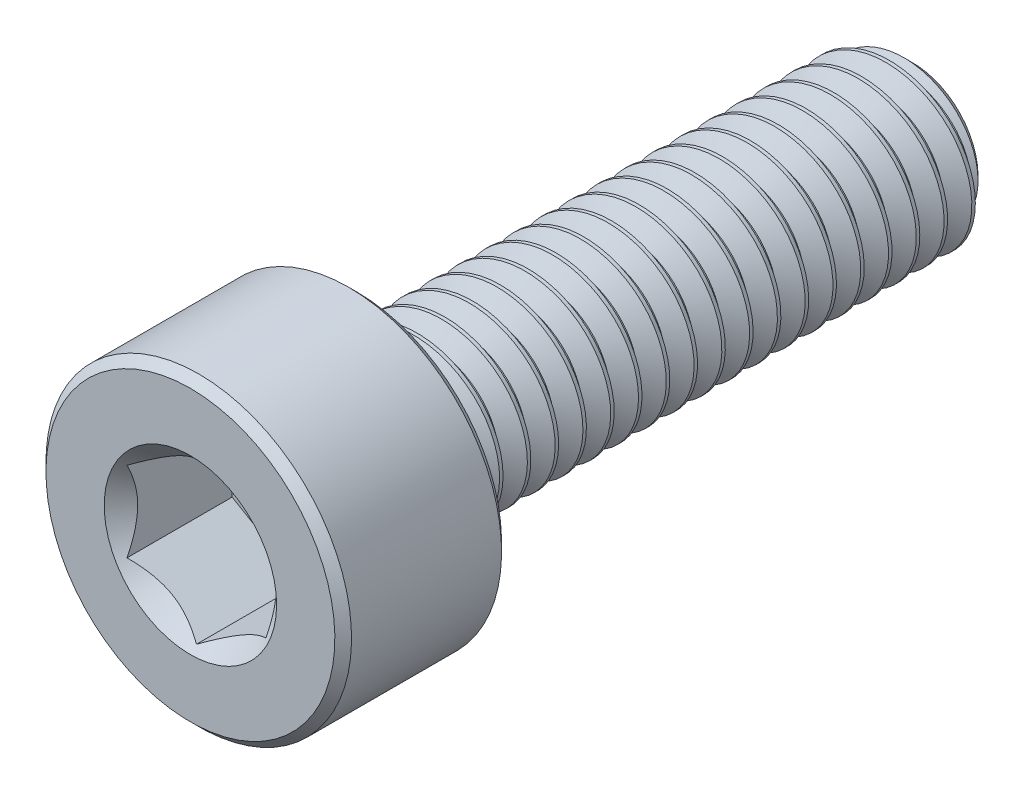
SolidWorks part; units mm, degrees
ref_plane "Front Plane" through (0, 0, 0) normal (0, 0, 1) x (1, 0, 0)
ref_plane "Top Plane" through (0, 0, 0) normal (0, 1, 0) x (1, 0, 0)
ref_plane "Right Plane" through (0, 0, 0) normal (1, 0, 0) x (0, 0, -1)
sketch "Sketch1" plane through (0, 0, 0) normal (1, 0, 0) x (0, 0, -1)
  line L0 (-6.5, 0) -> (6.5, 0) construction
  line L1 (6.5, 0) -> (6.5, 1.1752) construction
  line L2 (6.5, 1.1752) -> (6.1752, 1.5) construction
  line L3 (6.1752, 1.5) -> (6.125, 1.5) construction
  line L4 (6.125, 1.5) -> (-3.5, 1.5) construction
  line L5 (-3.5, 1.5) -> (-3.5, 2.75) construction
  line L6 (-3.5, 2.75) -> (-6.5, 2.75) construction
  line L7 (-6.5, 2.75) -> (-6.5, 0) construction
  line L8 (6.5, 1.1752) -> (6.5, 1.5) construction
  line L9 (6.4687, 1.5541) -> (6.7187, 1.1211) construction
  line L10 (6.7187, 1.1211) -> (6.9687, 1.5541) construction
  line L11 (6.9687, 1.5541) -> (6.4687, 1.5541) construction
  line L12 (6.7187, 1.5541) -> (6.7188, 1.5) construction
  line L13 (6.7187, 1.1211) -> (6.7187, 1.1752) construction
  line L14 (6.6875, 1.1752) -> (6.75, 1.1752) construction
  line L15 (6.5, 1.5) -> (6.9375, 1.5) construction
  line L16 (6.4844, 1.5271) -> (6.9531, 1.5271) construction
  line L17 (6.5, 0) -> (6.5, -1.5) construction
  line L18 (-3.65, 2.75) -> (-3.5, 2.6) construction
  line L19 (-6.35, 2.75) -> (-6.5, 2.6) construction
  line L20 (-3.5, 1.5) -> (-3.5, 0) construction
  line L21 (-3.5, 0.75) -> (-0.1667, 0.75) construction
  line L22 (-0.1667, 0.75) -> (3.1667, 0.75) construction
  line L23 (3.1667, 0.75) -> (6.5, 0.75) construction
  line L24 (-0.1667, 0.75) -> (-0.1667, 1.5) construction
  line L25 (-0.1667, 1.5) -> (-0.1667, 2.75) construction
  line L26 (3.1667, 0.75) -> (3.1667, 2.75) construction
  point P0 (-6.5, 1.25)
  point P3 (5.25, 1.5)
  point P4 (0, 0)
  point P18 (3.1667, 1.5)
  point P22 (6.7187, 1.1752)
  point P24 (6.125, 1.5)
  point P25 (6.7188, 1.5)
  point P28 (6.7188, 1.5271)
  point P29 (5.25, -1.5)
  point P30 (-0.1667, 1.5)
  point P31 (-5, 2.75)
  point P37 (-4.025, 2.75)
  point P38 (-6.275, 2.75)
  point P45 (-0.1667, 0.75)
  point P46 (3.1667, 0.75)
  dimension "D2" = 0.0625
  dimension "D7" = 0.15
  dimension "D8" = 0.15
  dimension "D9" = 0.15
  dimension "D10" = 0.075
  dimension "D11" = 0.375
  dimension "Drive Size" = 2.5
  dimension "Head Diameter" = 5.5
  dimension "Head Height" = 3
  dimension "Thread Pitch" = 0.5
  dimension "Thread Size" = 3
  dimension "Length" = 10
  dimension "D12" = 0.375
  dimension "D4" = 1.25
  dimension "D3" = 45
sketch "Sketch2" plane through (0, 0, 0) normal (1, 0, 0) x (0, 0, -1)
  line L0 (-6.5, 0) -> (-6.5, 2.6)
  line L1 (-6.35, 2.75) -> (-3.65, 2.75)
  line L2 (-3.5, 2.6) -> (-3.5, 1.65)
  line L4 (6.1752, 1.5) -> (6.5, 1.1752)
  line L5 (6.5, 1.1752) -> (6.5, 0)
  line L6 (-3.5, 2.75) -> (-6.5, 2.75) construction
  line L7 (6.5, 0) -> (-6.5, 0)
  line L8 (-6.35, 2.75) -> (-6.5, 2.6) construction
  line L10 (-6.35, 2.75) -> (-6.5, 2.6)
  line L14 (-3.65, 2.75) -> (-3.5, 2.6) construction
  line L16 (-3.65, 2.75) -> (-3.5, 2.6)
  line L17 (-3.5, 1.5) -> (-3.5, 2.75) construction
  line L19 (-3.35, 1.5) -> (6.1752, 1.5)
  line L20 (6.125, 1.5) -> (-3.5, 1.5) construction
  arc A1 (-3.5, 1.65) -> (-3.35, 1.5) centre (-3.35, 1.65) ccw
  dimension "D3" = 0.15
revolve "Revolve1" add sketch "Sketch2" angle 360 about L7
sketch "Sketch3" plane through (0, 0, 6.5) normal (0, 0, 1) x (1, 0, 0)
  line L1 (1.25, -0.7217) -> (1.25, 0.7217)
  line L2 (1.25, 0.7217) -> (0, 1.4434)
  line L3 (0, 1.4434) -> (-1.25, 0.7217)
  line L4 (-1.25, 0.7217) -> (-1.25, -0.7217)
  line L5 (-1.25, -0.7217) -> (0, -1.4434)
  line L6 (0, -1.4434) -> (1.25, -0.7217)
  circle A0 centre (0, 0) radius 1.25 construction
  circle A1 centre (0, 0) radius 2.75 construction
  circle A2 centre (0, 0) radius 2.75 construction
  circle A3 centre (0, 0) radius 1.4434 construction
  point P13 (0, 0)
  dimension "D1" = 2.8868
extrude "Cut-Extrude1" cut sketch "Sketch3" against normal offset from surface (2 mm away) 1 up to face at (0, 2.6, 3.5)
sketch "Sketch4" plane through (0, 0, 6.5) normal (0, 0, 1) x (1, 0, 0)
  circle A0 centre (0, 0) radius 1.5516
  dimension "D1" = 3.1033
extrude "Cut-Extrude2" cut sketch "Sketch4" against normal up to vertex (1.5 mm away) draft 45 up to point (0, 2.75, 5)
sketch "Sketch11" plane through (0, 0, 0) normal (1, 0, 0) x (0, 0, -1)
  line L0 (-6.5, 0) -> (6.5, 0) construction
  line L1 (-6.5, 0) -> (6.5, 0) construction
  line L2 (-1.625, 0) -> (-1.625, 1.5) construction
  line L3 (6.125, 1.5) -> (-3.5, 1.5) construction
  line L4 (4.625, 0) -> (4.625, 1.5) construction
  line L6 (6.5, 1.1752) -> (6.5, 1.5) construction
  point P2 (-1.625, 0)
  point P3 (4.625, 0)
  dimension "D1" = 1.875
  dimension "D2" = 1.875
sketch "Sketch6" plane through (0, 0, -6.5) normal (0, 0, -1) x (-1, 0, 0)
  circle A0 centre (0, 0) radius 1.5
curve "Helix/Spiral1" pitch 0.5 height 10.5 radius 1.5 centre (0, 0, -6.5) axis (0, 0, 1) start towards (0, 1, 0)
sketch "Sketch10" plane through (0, 0, 0) normal (1, 0, 0) x (0, 0, -1)
  line L0 (-3.35, -2.75) -> (-3.35, 2.75)
  line L5 (-6.5, 0) -> (6.5, 0) construction
  line L6 (-3.35, 1.5) -> (-3.35, -1.5) construction
  point P3 (-3.35, 0)
split "Split1" trim tools "Sketch10" bodies to split 106 resulting bodies 114 115
sketch "Sketch7" plane through (0, 0, 0) normal (1, 0, 0) x (0, 0, -1)
  line L0 (6.4844, 1.5271) -> (6.9531, 1.5271)
  line L1 (6.9531, 1.5271) -> (6.75, 1.1752)
  line L2 (6.75, 1.1752) -> (6.6875, 1.1752)
  line L3 (6.6875, 1.1752) -> (6.4844, 1.5271)
sweep "Cut-Sweep1" cut profiles "Sketch7" path "Helix/Spiral1" align with end faces yes
sketch "Sketch8" plane through (0, 0, 0) normal (1, 0, 0) x (0, 0, -1)
  line L0 (-3.5, 0) -> (-3.5, 1.5)
  line L1 (-3.35, -1.5) -> (-3.35, 1.5) construction
  line L2 (-3.5, 1.5) -> (-3.35, 1.5)
  line L4 (-3.35, 1.5) -> (-2.484, 0)
  line L5 (-2.484, 0) -> (-3.5, 0)
  line L6 (6.125, 1.5) -> (-3.5, 1.5) construction
  line L7 (-6.5, 0) -> (6.5, 0) construction
  dimension "D1" = 60
revolve "Revolve2" add sketch "Sketch8" angle 360 about L5
equation "\"D2@Sketch1\" = \"Thread Pitch@Sketch1\" / 8"
equation "\"D4@Helix/Spiral1\" = \"Thread Pitch@Sketch1\""
equation "\"D7@Sketch1\" = \"Head Height@Sketch1\" * .05"
equation "\"D8@Sketch1\"=\"D7@Sketch1\""
equation "\"D9@Sketch1\"=\"D7@Sketch1\""
equation "\"D10@Sketch1\"=\"D7@Sketch1\"/2"
equation "\"D11@Sketch1\"=\"D10@Sketch1\"*5"
equation "\"D4@Sketch1\"=\"Thread Pitch@Sketch1\"*2.5"
equation "\"D12@Sketch1\"=\"Thread Pitch@Sketch1\"*.75"
equation "\"D3@Helix/Spiral1\"=\"Length@Sketch1\"+\"Thread Pitch@Sketch1\""
equation "\"D3@Sketch2\"=\"Thread Size@Sketch1\"*0.05"
equation "\"D1@Sketch11\"=\"Length@Sketch1\"*0.1875"
equation "\"D2@Sketch11\"=\"D1@Sketch11\""
equation "\"D1@Sketch4\"=\"D1@Sketch3\"*1.075"
